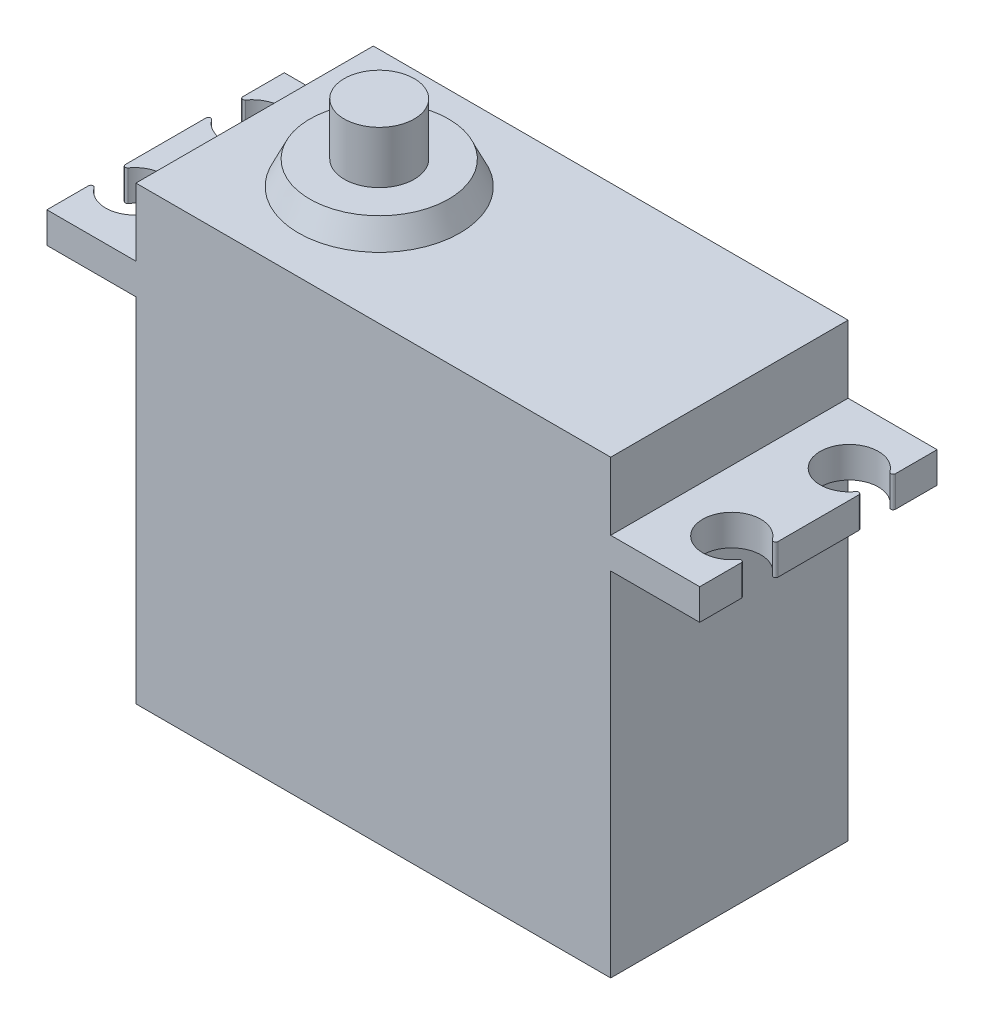
SolidWorks part; units mm, degrees
ref_plane "Plano frontal" through (0, 0, 0) normal (0, 0, 1) x (1, 0, 0)
ref_plane "Plano superior" through (0, 0, 0) normal (0, 1, 0) x (1, 0, 0)
ref_plane "Plano direito" through (0, 0, 0) normal (1, 0, 0) x (0, 0, -1)
sketch "Esboço1" plane through (0, 0, 0) normal (0, 0, 1) x (1, 0, 0)
  line L0 (0, 0) -> (0, 22.1597)
  line L5 (6.8, 0) -> (5.85, 2)
  line L6 (5.85, 2) -> (0, 2)
  line L7 (0, 2) -> (2.95, 2)
  line L8 (2.95, 2) -> (2.95, 6.4)
  line L9 (2.95, 6.4) -> (0, 6.4)
  line L10 (29.5, -5.7) -> (37, -5.7)
  line L11 (-10.5, 0) -> (29.5, 0)
  line L12 (-10.5, 0) -> (-10.5, -38)
  line L13 (-10.5, -38) -> (29.5, -38)
  line L14 (29.5, 0) -> (29.5, -38)
  line L15 (-10.5, -8.3) -> (-18, -8.3)
  line L16 (-10.5, -8.3) -> (-10.5, -5.7)
  line L17 (9.5, -38) -> (9.5, -22.5351) construction
  line L18 (-10.5, -5.7) -> (-18, -5.7)
  line L19 (-18, -8.3) -> (-18, -5.7)
  line L20 (37, -8.3) -> (37, -5.7)
  line L21 (29.5, -8.3) -> (37, -8.3)
  line L22 (29.5, -8.3) -> (29.5, -5.7)
  point P24 (37, -7)
  dimension "D1" = 6.8
  dimension "D2" = 2.95
  dimension "D3" = 5.85
  dimension "D4" = 2
  dimension "D5" = 4.4
  dimension "D6" = 13.45
  dimension "D7" = 40
  dimension "D8" = 38
  dimension "D9" = 5.7
  dimension "D10" = 55
  dimension "D11" = 2.6
extrude "Ressalto-extrusão1" add sketch "Esboço1" along normal mid plane 20 contours L14 L11 L12 L13 | L19 L15 L12 L18 | L14 L21 L20 L10 region at (9.5, -19, 0) region at (-14.25, -7, 0) region at (33.25, -7, 0)
revolve "Revolução1" add sketch "Esboço1<3>" angle 360 about L0 region at (3.1684, 0.975, 0) region at (1.475, 4.2, 0)
sketch "Esboço1<3>" plane through (0, 0, 0) normal (0, 0, 1) x (1, 0, 0) same geometry as "Esboço1"
sketch "Esboço3" plane through (0, -5.7, 0) normal (0, 1, 0) x (1, 0, 0)
  line L0 (9.5, 10) -> (9.5, -10) construction
  line L1 (-10.5, 10) -> (29.5, 10) construction
  line L2 (-10.5, -10) -> (29.5, -10) construction
  line L3 (-18, 0) -> (37, 0) construction
  line L4 (-18, -10) -> (-18, 10) construction
  line L5 (37, -10) -> (37, 10) construction
  line L6 (-15.65, 2.5) -> (-15.65, -2.5) construction
  line L7 (-13.2, 4.95) -> (-18, 4.95) construction
  circle A0 centre (-15.65, 4.95) radius 2.45
  circle A1 centre (-15.65, -4.95) radius 2.45
  circle A2 centre (34.65, -4.95) radius 2.45
  circle A3 centre (34.65, 4.95) radius 2.45
  dimension "D1" = 4.9
  dimension "D2" = 5
  dimension "D3" = 4.8
extrude "Corte-extrusão1" cut sketch "Esboço3" against normal through all
fillet "Filete1" radius 0.2 8 edges at (37, -7, 5.6428) (37, -7, -4.2572) (37, -7, 4.2572) (37, -7, -5.6428) (-18, -7, 4.2572) (-18, -7, 5.6428) (-18, -7, -4.2572) (-18, -7, -5.6428)
